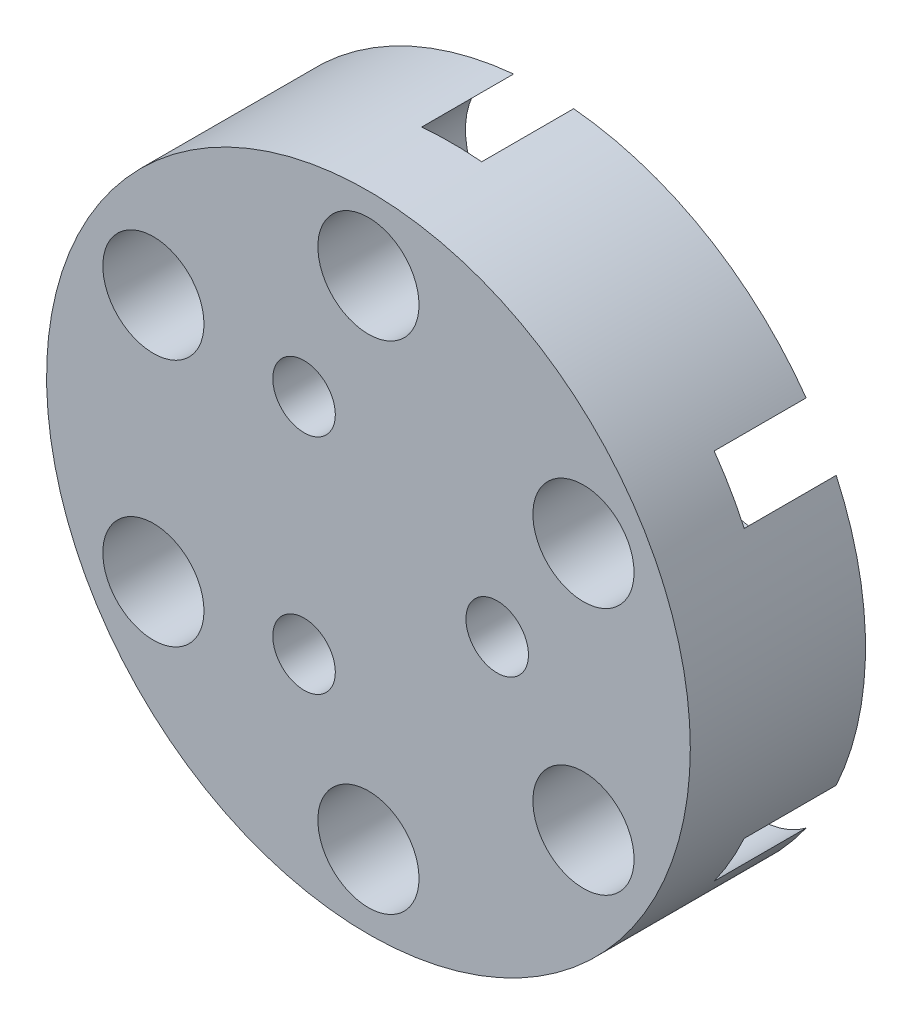
SolidWorks part; units mm, degrees
material "6061 Alloy"
ref_plane "Front Plane" through (0, 0, 0) normal (0, 0, 1) x (1, 0, 0)
ref_plane "Top Plane" through (0, 0, 0) normal (0, 1, 0) x (1, 0, 0)
ref_plane "Right Plane" through (0, 0, 0) normal (1, 0, 0) x (0, 0, -1)
sketch "Sketch1" plane through (0, 0, 0) normal (0, 0, 1) x (1, 0, 0)
  circle A0 centre (0, 0) radius 17.5
  dimension "D1" = 35
extrude "Boss-Extrude1" add sketch "Sketch1" along normal blind 9.525
sketch "Sketch2" plane through (0, 0, 9.525) normal (0, 0, 1) x (1, 0, 0)
  circle A0 centre (0, 0) radius 13.5 construction
  circle A1 centre (0, 13.5) radius 2.75
  circle A2 centre (11.6913, 6.75) radius 2.75
  circle A3 centre (11.6913, -6.75) radius 2.75
  circle A4 centre (0, -13.5) radius 2.75
  circle A5 centre (-11.6913, -6.75) radius 2.75
  circle A6 centre (-11.6913, 6.75) radius 2.75
  point P17 (0, 0)
  dimension "D1" = 27
  dimension "D2" = 5.5
  dimension "D3" = 6
extrude "M5_through" cut sketch "Sketch2" against normal up to surface (9.525 mm away) up to face at (17.5, 0, 0)
sketch "Sketch3" plane through (0, 0, 9.525) normal (0, 0, 1) x (1, 0, 0)
  line L0 (0, 0) -> (-3.5, 6.0622) construction
  line L1 (0, 0) -> (7, 0) construction
  circle A0 centre (0, 0) radius 7 construction
  circle A1 centre (-3.5, 6.0622) radius 1.7
  circle A2 centre (7, 0) radius 1.7
  circle A3 centre (-3.5, -6.0622) radius 1.7
  point P12 (0, 0)
  dimension "D1" = 14
  dimension "D3" = 3.4
  dimension "D4" = 3
  dimension "D2" = 120
extrude "M4_DRILL" cut sketch "Sketch3" against normal up to surface (9.525 mm away) up to face at (2.75, 13.5, 0)
sketch "Sketch4" plane through (0, 0, 0) normal (0, 0, -1) x (-1, 0, 0)
  circle A0 centre (0, 13.5) radius 4.25
  circle A1 centre (11.6913, 6.75) radius 4.25
  circle A2 centre (11.6913, -6.75) radius 4.25
  circle A3 centre (0, -13.5) radius 4.25
  circle A4 centre (-11.6913, -6.75) radius 4.25
  circle A5 centre (-11.6913, 6.75) radius 4.25
  point P15 (0, 0)
  dimension "D1" = 8.5
  dimension "D2" = 6
extrude "Cut-Extrude2" cut sketch "Sketch4" against normal blind 5
